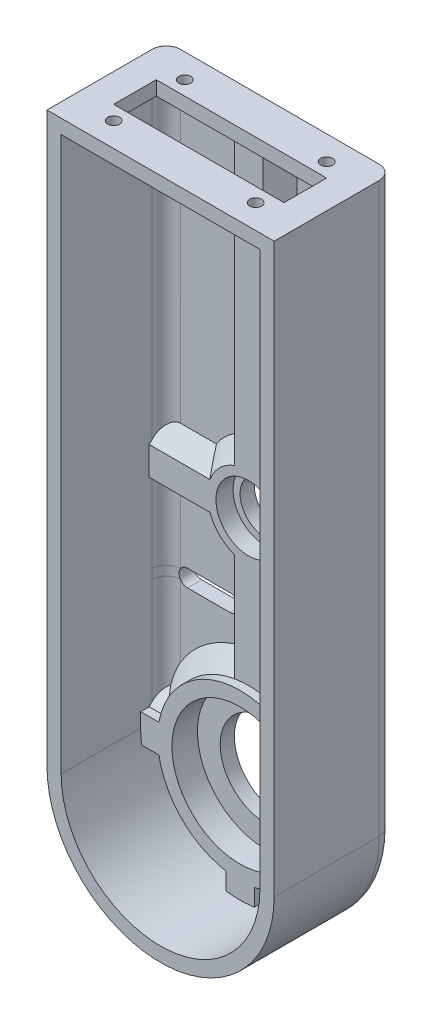
SolidWorks part; units mm, degrees
ref_plane "Plano frontal" through (0, 0, 0) normal (0, 0, 1) x (1, 0, 0)
ref_plane "Plano superior" through (0, 0, 0) normal (0, 1, 0) x (1, 0, 0)
ref_plane "Plano direito" through (0, 0, 0) normal (1, 0, 0) x (0, 0, -1)
sketch "Esboço1" plane through (0, 0, 0) normal (0, 0, 1) x (1, 0, 0)
  line L1 (-40, -100) -> (40, -100) construction
  line L2 (-40, -100) -> (-40, 100)
  line L3 (-40, 100) -> (40, 100)
  line L4 (40, -100) -> (40, 100)
  line L5 (-40, -100) -> (40, 100) construction
  line L6 (-40, 100) -> (40, -100) construction
  arc A0 (-40, -100) -> (40, -100) centre (0, -100) ccw
  circle A1 centre (0, -100) radius 16
  point P0 (0, 0)
  dimension "D3" = 32
  dimension "D1" = 80
  dimension "D2" = 200
extrude "Ressalto-extrusão1" add sketch "Esboço1" along normal blind 42
shell "Casca1" thickness 5 removed face at (0, -10, 42) removed face at (16, -100, 42)
sketch "Esboço3" plane through (0, 100, 0) normal (0, 1, 0) x (1, 0, 0)
  line L0 (0, -42) -> (0, 0) construction
  line L1 (40, -42) -> (-40, -42) construction
  line L2 (40, 0) -> (-40, 0) construction
  line L3 (40, -21) -> (-40, -21) construction
  line L4 (40, -42) -> (40, 0) construction
  line L5 (-40, -42) -> (-40, 0) construction
  line L7 (30, -13.5) -> (-30, -13.5)
  line L8 (30, -13.5) -> (30, -28.5)
  line L9 (30, -28.5) -> (-30, -28.5)
  line L10 (-30, -13.5) -> (-30, -28.5)
  line L11 (30, -13.5) -> (-30, -28.5) construction
  line L12 (30, -28.5) -> (-30, -13.5) construction
  line L13 (25, -8.5) -> (-25, -8.5) construction
  line L14 (25, -8.5) -> (25, -33.5) construction
  line L15 (25, -33.5) -> (-25, -33.5) construction
  line L16 (-25, -8.5) -> (-25, -33.5) construction
  line L17 (25, -8.5) -> (-25, -33.5) construction
  line L18 (25, -33.5) -> (-25, -8.5) construction
  circle A0 centre (25, -33.5) radius 2.1
  circle A1 centre (-25, -33.5) radius 2.1
  circle A2 centre (-25, -8.5) radius 2.1
  circle A3 centre (25, -8.5) radius 2.1
  point P12 (0, -21)
  point P17 (0, -21)
  dimension "D5" = 4.2
  dimension "D1" = 60
  dimension "D2" = 15
  dimension "D3" = 50
  dimension "D4" = 25
extrude "Corte-extrusão1" cut sketch "Esboço3" against normal up to surface (5 mm away) up to face at (0, 95, 23.5)
sketch "Esboço4" plane through (0, 0, 5) normal (0, 0, 1) x (1, 0, 0)
  circle A0 centre (0, -100) radius 24
  circle A1 centre (0, -100) radius 29
  dimension "D1" = 48
  dimension "D2" = 58
extrude "Ressalto-extrusão2" add sketch "Esboço4" along normal blind 9
sketch "Esboço5" plane through (0, 0, 5) normal (0, 0, 1) x (1, 0, 0)
  circle A0 centre (0, -20) radius 9
  circle A1 centre (0, -100) radius 16 construction
  dimension "D1" = 80
  dimension "D2" = 18
extrude "Corte-extrusão2" cut sketch "Esboço5" against normal up to surface (5 mm away) up to face at (0, -10, 0)
sketch "Esboço6" plane through (0, 0, 5) normal (0, 0, 1) x (1, 0, 0)
  circle A0 centre (0, -20) radius 11.5
  circle A1 centre (0, -20) radius 14.5
  dimension "D1" = 23
  dimension "D2" = 29
extrude "Ressalto-extrusão3" add sketch "Esboço6" along normal blind 6
sketch "Esboço7" plane through (0, 0, 14) normal (0, 0, 1) x (1, 0, 0)
  line L0 (29, -100) -> (35, -100)
  line L1 (-29, -100) -> (-35, -100)
  line L2 (0, -129) -> (0, -135)
  circle A0 centre (0, -100) radius 29 construction
  circle A1 centre (0, -100) radius 29 construction
  arc A2 (-35, -100) -> (35, -100) centre (0, -100) ccw construction
rib "Nervura1" sketch "Esboço7" sketch "Esboço7" thickness 10 extrusion direction normal to sketch draft on no parameters "D1"=10
sketch "Esboço8" plane through (0, 0, 11) normal (0, 0, 1) x (1, 0, 0)
  line L0 (14.5, -20) -> (35, -20)
  line L1 (35, -95) -> (35, 95) construction
  line L2 (-14.5, -20) -> (-35, -20)
  line L3 (-35, 95) -> (-35, -100) construction
  line L4 (0, -5.5) -> (0, 95)
  line L5 (35, 95) -> (-35, 95) construction
  line L6 (0, -34.5) -> (0, -71)
  circle A0 centre (0, -20) radius 14.5 construction
  circle A1 centre (0, -20) radius 14.5 construction
  arc A2 (28.5657, -95) -> (-28.5657, -95) centre (0, -100) ccw construction
rib "Nervura2" sketch "Esboço8" sketch "Esboço8" thickness 10 extrusion direction normal to sketch draft on no parameters "D1"=10
sketch "Esboço9" plane through (0, 0, 5) normal (0, 0, 1) x (1, 0, 0)
  line L0 (-27.5, -55) -> (-12.5, -55) construction
  line L1 (-27.5, -52) -> (-12.5, -52)
  line L2 (-27.5, -58) -> (-12.5, -58)
  line L3 (-40, 100) -> (-40, -100) construction
  line L4 (0, -100) -> (0, -84) construction
  arc A0 (-27.5, -52) -> (-27.5, -58) centre (-27.5, -55) ccw
  arc A1 (-12.5, -58) -> (-12.5, -52) centre (-12.5, -55) ccw
  circle A2 centre (0, -100) radius 16 construction
  point P2 (-20, -55)
  dimension "D2" = 3
  dimension "D1" = 20
  dimension "D3" = 15
  dimension "D4" = 45
extrude "Corte-extrusão3" cut sketch "Esboço9" against normal up to surface (5 mm away) up to face at (16, -100, 0)
sketch "Esboço10" plane through (0, 0, 5) normal (0, 0, 1) x (1, 0, 0)
  line L0 (0, -100) -> (35, -45.2277) construction
  line L2 (35, -95) -> (35, -25) construction
  line L3 (0, -100) -> (35, -51.266) construction
  line L7 (14.6835, -56.3488) -> (22.2163, -49.7717)
  line L8 (21.5385, -66.294) -> (28.6945, -60.0457) construction
  line L9 (22.2163, -49.7717) -> (19.5854, -46.7586)
  line L10 (19.5854, -46.7586) -> (12.0527, -53.3357)
  line L11 (12.0527, -53.3357) -> (14.6835, -56.3488)
  circle A0 centre (21.5385, -66.294) radius 1.2
  circle A1 centre (28.6945, -60.0457) radius 1.2
  dimension "D1" = 9.5
  dimension "D2" = 2.4
  dimension "D3" = 40
  dimension "D4" = 65
  dimension "D5" = 60
  dimension "D6" = 10
  dimension "D7" = 12
  dimension "D8" = 4
extrude "Corte-extrusão4" cut sketch "Esboço10" against normal up to surface (5 mm away) up to face at (-20, -55, 0)
ref_plane "Plano1" through (0, -65, 0) normal (0, -1, 0) x (-1, 0, 0)
sketch "Esboço11" plane through (0, -65, 0) normal (0, -1, 0) x (-1, 0, 0)
  line L0 (-40, -21) -> (-31, -21)
  line L1 (-40, -42) -> (-40, 0) construction
  line L2 (-31, -21) -> (-31, -36)
  line L3 (-31, -36) -> (-33, -36)
  line L4 (-33, -36) -> (-33, -26)
  line L5 (-33, -26) -> (-40, -26)
  line L6 (-40, -26) -> (-40, -21)
  dimension "D1" = 9
  dimension "D2" = 7
  dimension "D3" = 15
  dimension "D4" = 10
extrude "Ressalto-extrusão4" add sketch "Esboço11" along normal blind 4
fillet "Filete1" radius 1.5 3 edges at (31, -67, 21) (31, -67, 36) (33, -67, 36)
pattern_linear "Padrão linear1" count 3 spacing 65 along (0, 1, 0) of "Filete1", "Ressalto-extrusão4"
chamfer "Chanfro1" distance 6 angle 45 22 edges at (-31.6034, -105, 5) (5, -131.6034, 5) (-5, -131.6034, 5) (31.6034, -105, 5) (-20.5061, -120.5061, 5) (20.5061, -120.5061, 5) (20.5061, -79.4939, 5) (-20.5061, -79.4939, 5) (31.7829, -95, 5) (24.3053, -25, 5) (5, -52.5225, 5) (-10.253, -30.253, 5) (10.253, -30.253, 5) (-10.253, -9.747, 5) (10.253, -9.747, 5) (-31.7829, -95, 5) (-5, -52.5225, 5) (-24.3053, -25, 5) (24.3053, -15, 5) (5, 44.3053, 5) (-24.3053, -15, 5) (-5, 44.3053, 5)
fillet "Filete2" radius 5 4 edges at (35, -60, 5) (-35, -60, 5) (-35, 43, 5) (35, 43, 5)
fillet "Filete3" radius 5 3 edges at (-40, 0, 0) (0, -140, 0) (40, 0, 0)
